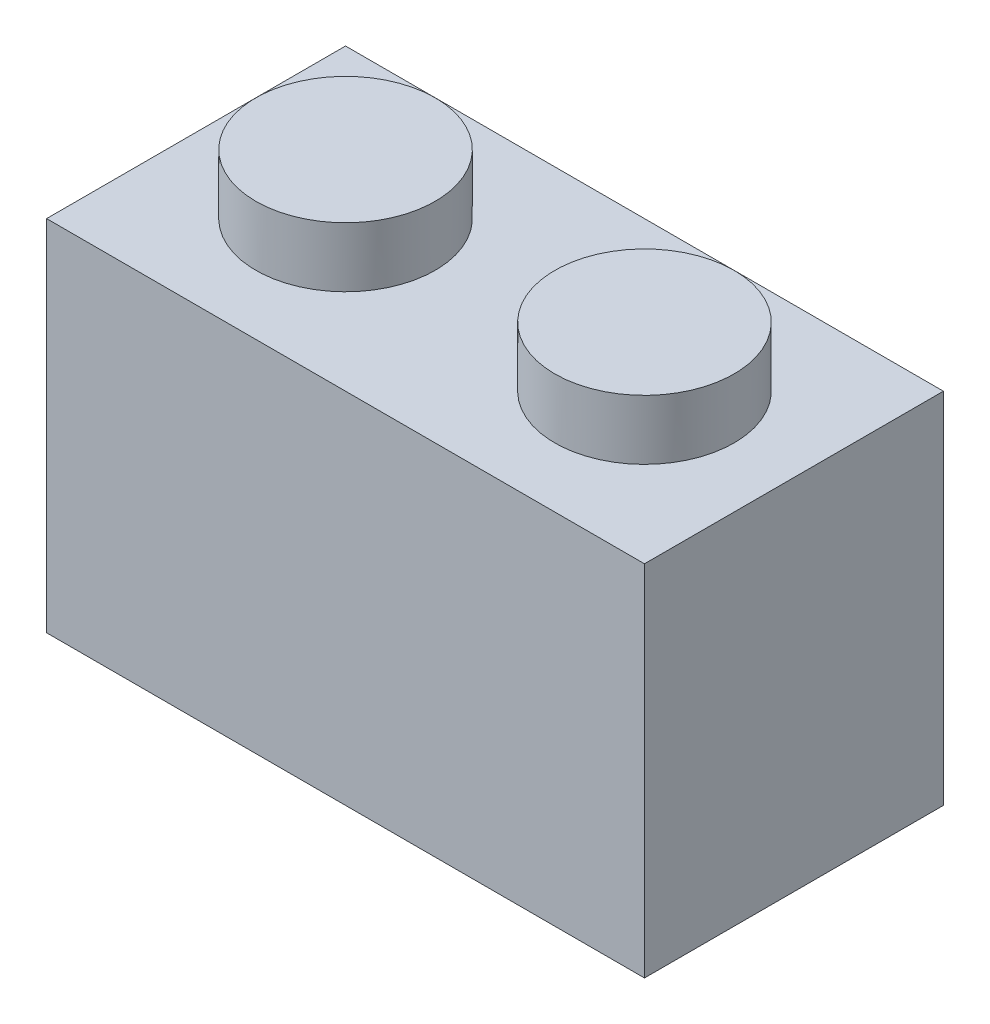
SolidWorks part; units mm, degrees
ref_plane "Front Plane" through (0, 0, 0) normal (0, 0, 1) x (1, 0, 0)
ref_plane "Top Plane" through (0, 0, 0) normal (0, 1, 0) x (1, 0, 0)
ref_plane "Right Plane" through (0, 0, 0) normal (1, 0, 0) x (0, 0, -1)
sketch "Sketch1" plane through (0, 0, 0) normal (0, 1, 0) x (1, 0, 0)
  line L1 (-5, 2.5) -> (5, 2.5)
  line L2 (-5, 2.5) -> (-5, -2.5)
  line L3 (-5, -2.5) -> (5, -2.5)
  line L4 (5, 2.5) -> (5, -2.5)
  line L5 (-5, 2.5) -> (5, -2.5) construction
  line L6 (-5, -2.5) -> (5, 2.5) construction
  line L7 (-4, -1.5) -> (4, -1.5)
  line L8 (-4, -1.5) -> (-4, 1.5)
  line L9 (-4, 1.5) -> (4, 1.5)
  line L10 (4, -1.5) -> (4, 1.5)
  line L11 (-4, -1.5) -> (4, 1.5) construction
  line L12 (-4, 1.5) -> (4, -1.5) construction
  circle A0 centre (-2.5, 0) radius 1.5
  circle A1 centre (2.5, 0) radius 1.5
  circle A2 centre (-2.5, 0) radius 0.75
  circle A3 centre (2.5, 0) radius 0.75
  circle A4 centre (0, 0) radius 1
  point P0 (0, 0)
  point P6 (0, 0)
  dimension "D5" = 1.5
  dimension "D1" = 5
  dimension "D2" = 10
  dimension "D3" = 1
  dimension "D4" = 1
  dimension "D6" = 2
extrude "Boss-Extrude1" add sketch "Sketch1" along normal blind 2 contours A0 A2 | A2 | A3 | A1 A3 region at (-3.5307, 0, 1.0307) region at (1.4693, 0, 1.0307) region at (-2.5, 0, 0) region at (2.5, 0, 0)
extrude "Boss-Extrude2" add sketch "Sketch1<3>" along normal blind 1 contours L2 L3 L4 L1
sketch "Sketch1<3>" plane through (0, 0, 0) normal (0, 1, 0) x (1, 0, 0) same geometry as "Sketch1"
extrude "Cut-Extrude1" cut sketch "Sketch1<4>" along normal blind 1 contours A2 | A3 region at (-2.5, 0, 0) region at (2.5, 0, 0)
sketch "Sketch1<4>" plane through (0, 0, 0) normal (0, 1, 0) x (1, 0, 0) same geometry as "Sketch1"
extrude "Boss-Extrude3" add sketch "Sketch1<5>" against normal blind 5 contours A4 | L4 L1 L2 L3 L10 L7 L8 L9 region at (0, 0, -2.3882) region at (0, 0, 0)
sketch "Sketch1<5>" plane through (0, 0, 0) normal (0, 1, 0) x (1, 0, 0) same geometry as "Sketch1"
